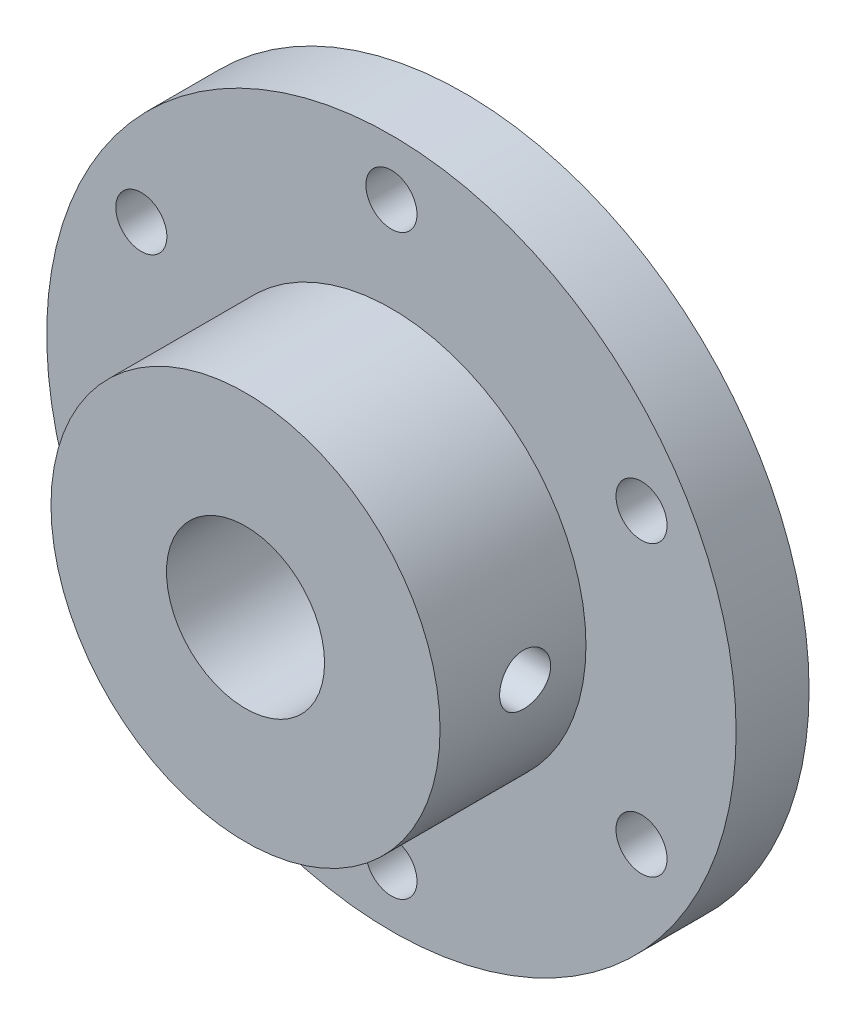
SolidWorks part; units mm, degrees
material "6061 合金"
ref_plane "前基準面" through (0, 0, 0) normal (0, 0, 1) x (1, 0, 0)
ref_plane "上基準面" through (0, 0, 0) normal (0, 1, 0) x (1, 0, 0)
ref_plane "右基準面" through (0, 0, 0) normal (1, 0, 0) x (0, 0, -1)
sketch "草圖1" plane through (0, 0, 0) normal (0, 0, 1) x (1, 0, 0)
  circle A0 centre (0, 0) radius 28.35
  dimension "D1" = 56.7
extrude "填料-伸長1" add sketch "草圖1" along normal blind 6
sketch "草圖2" plane through (0, 0, 6) normal (0, 0, 1) x (1, 0, 0)
  circle A0 centre (0, 0) radius 16
  dimension "D1" = 32
extrude "填料-伸長2" add sketch "草圖2" along normal blind 12
sketch "草圖3" plane through (0, 0, 18) normal (0, 0, 1) x (1, 0, 0)
  circle A0 centre (0, 0) radius 6.5
  dimension "D1" = 13
extrude "除料-伸長1" cut sketch "草圖3" against normal through all
hole_wizard "M5 螺紋孔2" positions "草圖7" profile "草圖8" tap size "M5" standard "ISO" end condition through all
sketch "草圖7" plane through (0, 0, 0) normal (0, 0, -1) x (-1, 0, 0)
  line L0 (0, 0) -> (0, 23.75) construction
  point P0 (0, 23.75)
  dimension "D1" = 23.75
sketch "草圖8" plane through (0, 23.75, 0) normal (1, 0, 0) x (0, 1, 0)
  line L0 (0, 0) -> (0, 18)
  line L1 (0, 18) -> (2.1, 18)
  line L2 (2.1, 18) -> (2.1, 0)
  line L5 (2.1, 0) -> (0, 0)
  line L11 (0, -6.35) -> (0, 107.95) construction
  dimension "貫穿螺孔鑽直徑" = 4.2
  dimension "貫穿螺孔鑽深度" = 18
pattern_circular "環狀複製排列1" count 6 over 360 about axis through (0, 0, 6) along (0, 0, 1) of "M5 螺紋孔2"
ref_plane "平面1" through (16, 0, 0) normal (1, 0, 0) x (0, 0, -1)
sketch "草圖6" plane through (16, 0, 0) normal (1, 0, 0) x (0, 0, -1)
  line L0 (-18, 0) -> (-6, 0) construction
  line L2 (-18, 16) -> (-18, -16) construction
  line L3 (-6, 28.35) -> (-6, -28.35) construction
  circle A0 centre (-11, 0) radius 2.1
  dimension "D2" = 4.2
  dimension "D1" = 5
extrude "除料-伸長3" cut sketch "草圖6" against normal up to next
ref_axis "基準軸1" through (6.0257, 0, 11) along (1, 0, 0)
